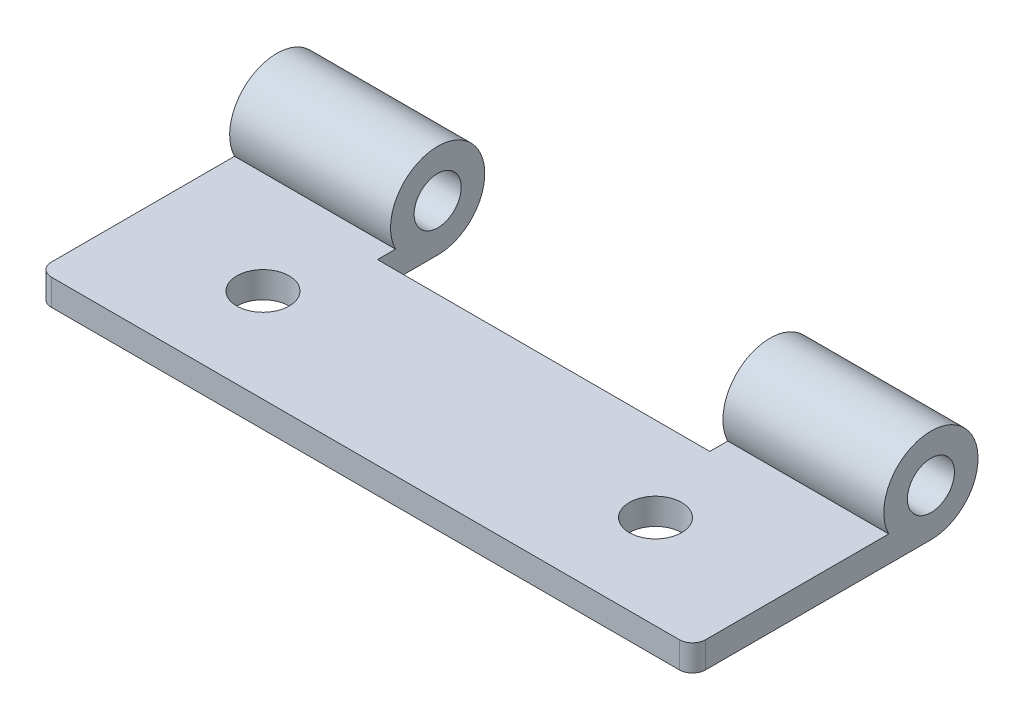
SolidWorks part; units mm, degrees
ref_plane "Front Plane" through (0, 0, 0) normal (0, 0, 1) x (1, 0, 0)
ref_plane "Top Plane" through (0, 0, 0) normal (0, 1, 0) x (1, 0, 0)
ref_plane "Right Plane" through (0, 0, 0) normal (1, 0, 0) x (0, 0, -1)
sketch "Sketch2" plane through (0, 0, 0) normal (1, 0, 0) x (0, 0, -1)
  line L0 (0, -1.8) -> (-9.1125, -1.8)
  line L1 (-9.1125, -1.8) -> (-9.1125, -0.8)
  line L2 (-9.1125, -0.8) -> (-1.6125, -0.8)
  arc A0 (0, -1.8) -> (-1.6125, -0.8) centre (0, 0) ccw
  dimension "D1" = 3.6
  dimension "D2" = 7.5
  dimension "D3" = 1
extrude "Boss-Extrude1" add sketch "Sketch2" along normal blind 25
sketch "Sketch3" plane through (0, 0, 0) normal (0, 1, 0) x (1, 0, 0)
  line L0 (12.5, -9.1125) -> (12.5, 1.8)
  line L1 (6.15, 2.5152) -> (18.85, 2.5152)
  line L2 (6.15, 2.5152) -> (6.15, -2.3)
  line L3 (6.15, -2.3) -> (18.85, -2.3)
  line L4 (18.85, 2.5152) -> (18.85, -2.3)
  line L5 (6.15, 2.5152) -> (18.85, -2.3) construction
  line L6 (6.15, -2.3) -> (18.85, 2.5152) construction
  line L7 (25, -9.1125) -> (0, -9.1125) construction
  line L8 (25, 1.8) -> (0, 1.8) construction
  point P4 (12.5, 0.1076)
  dimension "D1" = 4.1
  dimension "D2" = 12.7
extrude "Cut-Extrude1" cut sketch "Sketch3" against normal blind 25 and the other way blind 25 contours L4 L1 L2 L3 region at (12.5, 0, -2.3794)
ref_plane "Plane1" through (25, 0, 0) normal (1, 0, 0) x (0, 0, -1)
sketch "Sketch4" plane through (25, 0, 0) normal (1, 0, 0) x (0, 0, -1)
  circle A0 centre (0, 0) radius 0.9
  dimension "D1" = 1.8
extrude "Cut-Extrude2" cut sketch "Sketch4" against normal blind 25
fillet "Fillet1" radius 0.5 2 edges at (0, -1.3, 9.1125) (25, -1.3, 9.1125)
sketch "Sketch5" plane through (0, 0, 0) normal (0, 1, 0) x (1, 0, 0)
  line L0 (5, -9.1125) -> (5, -5.526)
  line L1 (24.5, -9.1125) -> (0.5, -9.1125) construction
  line L2 (0, -1.6125) -> (0, -8.6125) construction
  line L3 (12.5, -9.1125) -> (12.5, -2.3) construction
  line L4 (6.15, -2.3) -> (18.85, -2.3) construction
  circle A0 centre (5, -5.526) radius 1
  circle A1 centre (20, -5.526) radius 1
  point P4 (5, -7.3192)
  dimension "D1" = 5
extrude "Cut-Extrude3" cut sketch "Sketch5" against normal blind 25 and the other way blind 25 contours A0 | A1 region at (5.6871, 0, 6.2131) region at (20, 0, 5.526)
